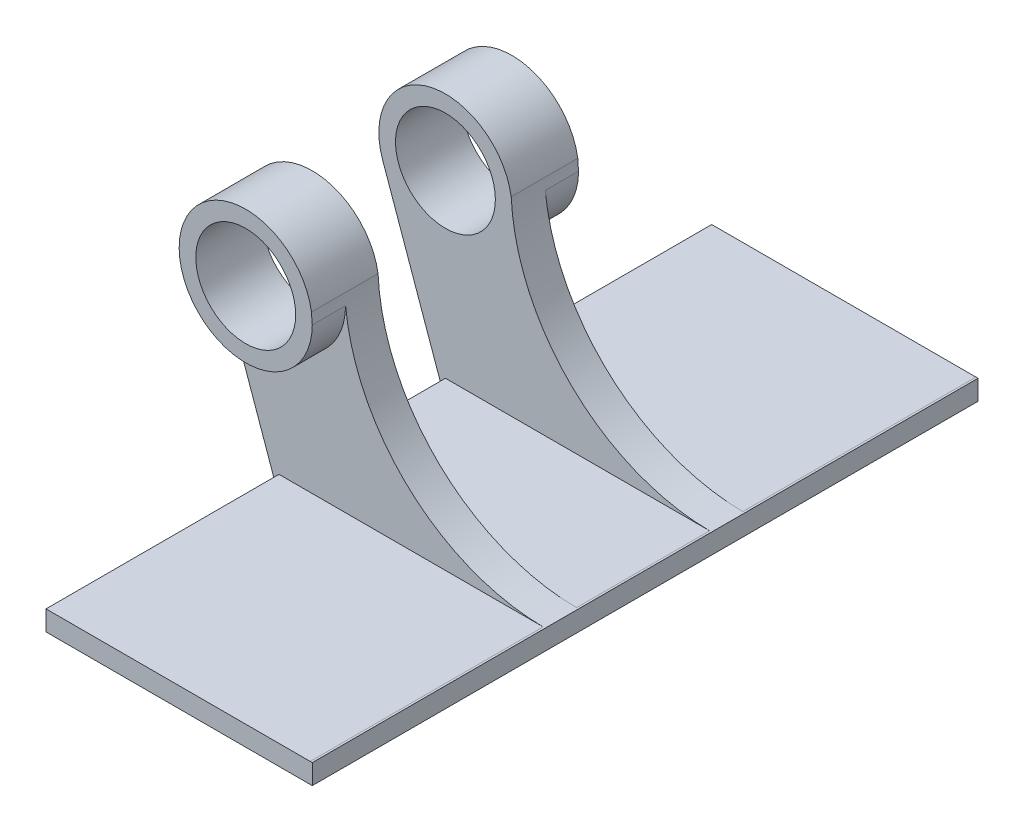
SolidWorks part; units mm, degrees
ref_plane "Alzado" through (0, 0, 0) normal (0, 0, 1) x (1, 0, 0)
ref_plane "Planta" through (0, 0, 0) normal (0, 1, 0) x (1, 0, 0)
ref_plane "Vista lateral" through (0, 0, 0) normal (1, 0, 0) x (0, 0, -1)
sketch "Croquis2" plane through (0, 0, 0) normal (0, 0, 1) x (1, 0, 0)
  line L0 (0, 0) -> (0, -30) construction
  line L1 (40, -30) -> (0, -30)
  line L2 (40, -30) -> (40, -27)
  line L3 (40, -27) -> (0, -27)
  line L4 (0, -30) -> (0, -27)
  line L5 (40, -30) -> (0, -27) construction
  line L6 (40, -27) -> (0, -30) construction
  line L7 (0, -30) -> (-9.4281, -3.3333)
  circle A0 centre (0, 0) radius 10
  arc A1 (40, -27) -> (9.8784, 1.5545) centre (39.8436, 2.9996) cw
  circle A2 centre (0, 0) radius 7.5
  point P3 (20, -28.5)
  dimension "D1" = 20
  dimension "D5" = 30
  dimension "D7" = 15
  dimension "D2" = 3
  dimension "D3" = 30
  dimension "D4" = 40
  dimension "D6" = 39.8436
extrude "Saliente-Extruir1" add sketch "Croquis2" along normal blind 10 contours A0 A1 A2 region at (-2.3848, 9.42, 0)
extrude "Saliente-Extruir2" add sketch "Croquis2<4>" along normal blind 5 contours L3 A1 A0 L7 L4 region at (8.5771, -18.3272, 0)
sketch "Croquis2<4>" plane through (0, 0, 0) normal (0, 0, 1) x (1, 0, 0) same geometry as "Croquis2"
ref_plane "Plano1" through (0, 0, -10) normal (0, 0, -1) x (-1, 0, 0)
extrude "Saliente-Extruir3" add sketch "Croquis2<6>" along normal blind 40 contours L2 A1 L3 L4 L1 region at (20, -28.5, 0)
sketch "Croquis2<6>" plane through (0, 0, 0) normal (0, 0, 1) x (1, 0, 0) same geometry as "Croquis2"
mirror "Simetría2" about plane through (0, 0, -10) normal (0, 0, -1) of bodies 104 102
extrude "Saliente-Extruir4" add sketch "Croquis2<7>" along direction (0, 0, -1) on the side against the normal up to surface (20 mm away) contours L2 A1 L3 L4 L1 region at (20, -28.5, 0) up to face at (7.5, 0, -20)
sketch "Croquis2<7>" plane through (0, 0, 0) normal (0, 0, 1) x (1, 0, 0) same geometry as "Croquis2"
